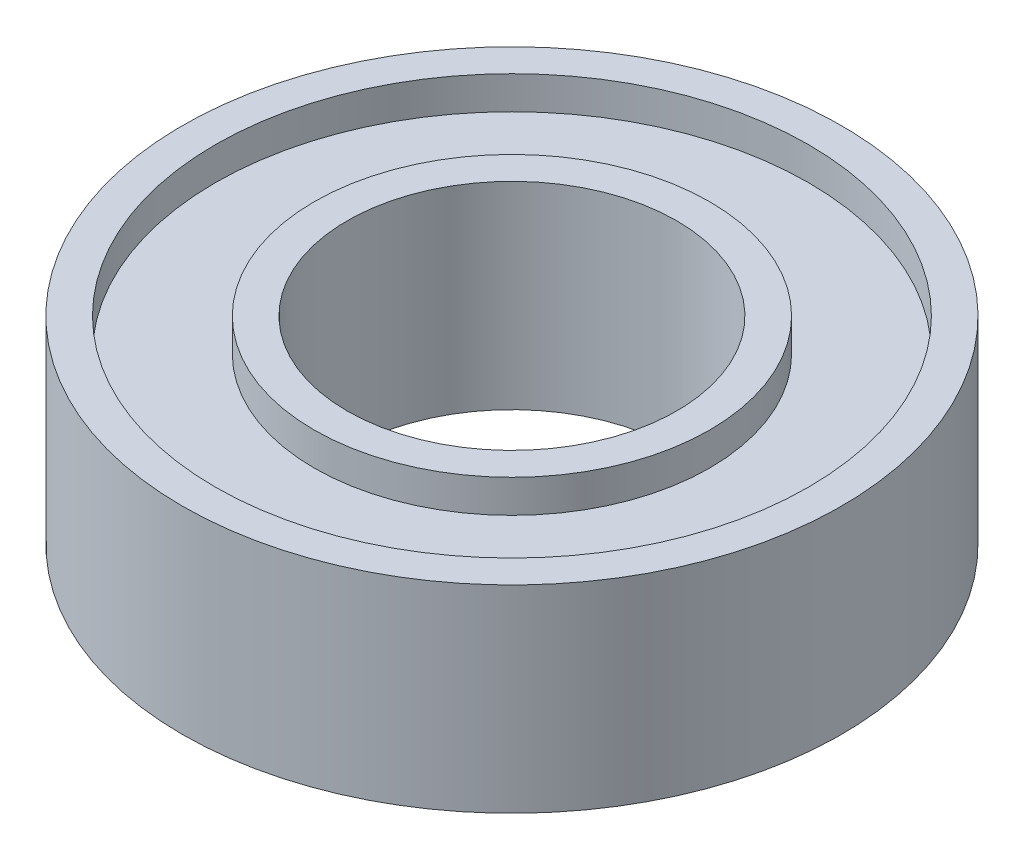
SolidWorks part; units mm, degrees
material "Chrome Stainless Steel"
ref_plane "Front Plane" through (0, 0, 0) normal (0, 0, 1) x (1, 0, 0)
ref_plane "Top Plane" through (0, 0, 0) normal (0, 1, 0) x (1, 0, 0)
ref_plane "Right Plane" through (0, 0, 0) normal (1, 0, 0) x (0, 0, -1)
sketch "Sketch1" plane through (0, 0, 0) normal (0, 1, 0) x (1, 0, 0)
  circle A0 centre (0, 0) radius 10
  dimension "D1" = 20
extrude "main extrusion" add sketch "Sketch1" along normal blind 6 contours A0
sketch "Sketch2" plane through (0, 6, 0) normal (0, 1, 0) x (1, 0, 0)
  circle A0 centre (0, 0) radius 5
  dimension "D1" = 10
extrude "ID bore" cut sketch "Sketch2" against normal blind 20
sketch "Sketch3" plane through (0, 6, 0) normal (0, 1, 0) x (1, 0, 0)
  circle A0 centre (0, 0) radius 9
  circle A1 centre (0, 0) radius 6
  dimension "D1" = 12
  dimension "D2" = 18
extrude "seal recess" cut sketch "Sketch3" against normal blind 1
equation "\"D1@Sketch1\"=\"bearing OD\""
equation "\"D1@main extrusion\" = \"bearing depth\""
equation "\"D1@Sketch2\"=\"bearing ID\""
equation "\"bearing OD\" = 20mm"
equation "\"bearing outer race thickness\"= 1mm"
equation "\"bearing ID\"= 10mm"
equation "\"bearing depth\"= 6mm"
equation "\"bearing inner race thickness\"= 1mm"
equation "\"seal OD\" = 20mm"
equation "\"seal ID\"= 8mm"
equation "\"seal depth\"= 6mm"
equation "\"motor to housing distance\"= 60mm"
equation "\"motor mount pattern diameter\"= 30mm"
equation "\"motor mount coupler shaft hole diameter\"= \"coupler shaft base diameter\"+ 4mm"
equation "\"motor mount to housing m8 screw hole diameter\"= 8.5mm"
equation "\"motor mount to housing m8 screw post radius\"= ( 3 * \"motor mount to housing m8 screw hole diameter\" ) / 2"
equation "\"motor mount to housing m8 pattern diameter\"= 100mm"
equation "\"motor mount to housing m4 screw hole diamater\"= 4mm"
equation "\"motor mount to housing m4 head diameter\"= 7.25mm"
equation "\"motor mount to housing m4 head depth\"= 4mm"
equation "\"motor mount plate thickness\"= 6mm + \"motor mount to housing m4 head depth\""
equation "\"motor mount m6 screw hole diameter\"= 6.5mm"
equation "\"motor mount m6 screw socket head diameter\"= 10.5mm"
equation "\"motor mount m6 screw socket head depth\"= 6mm"
equation "\"motor shaft pride\"= 32mm"
equation "\"motor shaft flat section length from tip\"= 25.7mm"
equation "\"motor shaft bore end clearance\"= 2mm"
equation "\"motor mount shaft hole depth\"= \"motor shaft pride\""
equation "\"coupler shaft set screw drill hole diameter\"= 6mm"
equation "\"coupler shaft motor shaft hole diameter\"= 8mm"
equation "\"coupler shaft base diameter\"= 18mm"
equation "\"coupler shaft base length\"= \"motor mount shaft hole depth\" + 10mm"
equation "\"coupler shaft second section diameter\"= \"bearing ID\" + \"bearing inner race thickness\" * 2"
equation "\"coupler shaft third section diamater\"= \"bearing ID\""
equation "\"coupler shaft second section length\"= \"motor to housing distance\" -  \"coupler shaft base length\" - 2mm"
equation "\"coupler shaft set screw 1 distance\"= \"motor mount shaft hole depth\" / 3"
equation "\"coupler shaft set screw 2 distance\"= \"motor mount shaft hole depth\" * 4 / 5"
equation "\"housing bearing seat lip thickness\" = 2mm"
equation "\"housing base thickness\"= \"housing bearing seat lip thickness\" + \"seal depth\" + \"bearing depth\""
equation "\"impeller base outer diameter\"= 1.75in"
equation "\"impeller base outer thickness\"= 1mm"
equation "\"impeller base center thickness\"= 5mm"
equation "\"impeller number of vanes\"= 8"
equation "\"impeller vane outer height`\"= 4mm"
equation "\"impeller vane inner height\"= 8mm"
equation "\"impeller primary vane opening diamater\"= 10mm"
equation "\"impeller shaft bore size\"=4mm "
equation "\"impeller vane inner thickness\"= .75mm"
equation "\"impeller vane outer thickness\"= 1.5mm"
equation "\"impeller primary vane entrance angle\"= 20deg"
equation "\"impeller secondary vane entrance angle\"= 20deg"
equation "\"impeller secondary vane opening diameter\"= 10mm"
equation "\"housing top impeller vertical clearance\"= 1mm"
equation "\"housing top impeller horizontal clearance\"= 1mm"
equation "\"housing top impeller bottom clearance\"= 2mm"
equation "\"housing top impeller cavity height\"= \"housing top impeller bottom clearance\" + \"impeller base center thickness\" + \"impeller vane inner height\" + \"housing top impeller vertical clearance\""
equation "\"housing top impeller cavity diameter\"= 2 * \"housing top impeller horizontal clearance\" + \"impeller base outer diameter\""
equation "\"housing top impeller cavity tip height\"= \"housing top impeller bottom clearance\" + \"housing top impeller vertical clearance\" + \"impeller base outer thickness\" + \"impeller vane outer height\""
equation "\"housing top entrance OD\"= 20mm"
equation "\"housing top exit OD\"= 5mm"
equation "\"housing top o-ring channel height\"= 1.5mm"
equation "\"housing top o ring channel width\"= 1.5mm"
equation "\"housing top threaded inlet depth\"= 8mm"
equation "\"housing top total thickness\"= \"housing top threaded inlet depth\" + \"housing top impeller cavity height\""
equation "\"housing top total width\"= 10mm"
equation "\"housing top exit threaded diameter\"= 8mm"
equation "\"housing top exit threaded depth\"= 8mm"
equation "\"D2@Sketch3\"=\"bearing OD\"-\"bearing outer race thickness\"*2"
equation "\"D1@Sketch3\"=\"bearing ID\"+\"bearing inner race thickness\"*2"
